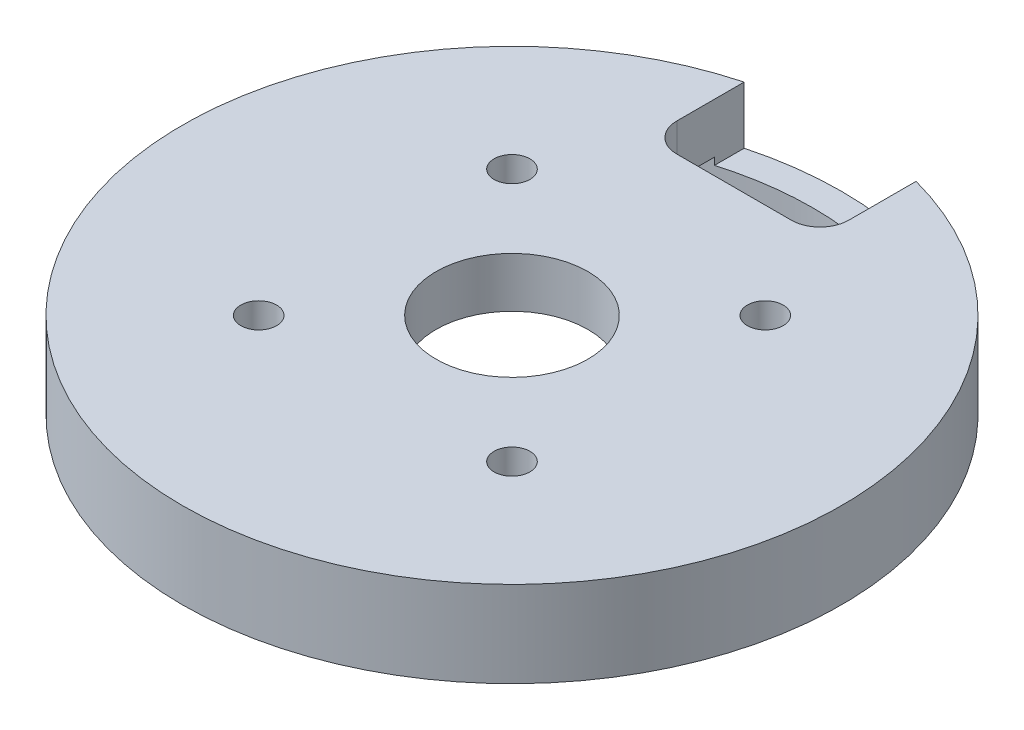
SolidWorks part; units mm, degrees
material "3.1355 (EN-AW 2024)"
ref_plane "Спереди" through (0, 0, 0) normal (0, 0, 1) x (1, 0, 0)
ref_plane "Сверху" through (0, 0, 0) normal (0, 1, 0) x (1, 0, 0)
ref_plane "Справа" through (0, 0, 0) normal (1, 0, 0) x (0, 0, -1)
sketch "Эскиз1" plane through (0, 0, 0) normal (0, 1, 0) x (1, 0, 0)
  circle A0 centre (0, 0) radius 23
  dimension "D1" = 46
extrude "Бобышка-Вытянуть1" add sketch "Эскиз1" along normal blind 6
sketch "Эскиз2" plane through (0, 0, 0) normal (0, -1, 0) x (1, 0, 0)
  circle A1 centre (0, 0) radius 5.3
  circle A2 centre (0, 0) radius 21
  circle A3 centre (0, 0) radius 21
  dimension "D2" = 10.6
  dimension "D1" = 2
extrude "Вырез-Вытянуть1" cut sketch "Эскиз2" against normal blind 2.5 contours A3 A1 | A1 region at (0, 0, 0) region at (-20.406, 0, 0)
extrude "Вырез-Вытянуть2" cut sketch "Эскиз2<3>" against normal through all contours A1 region at (0, 0, 0)
sketch "Эскиз2<3>" plane through (0, 0, 0) normal (0, -1, 0) x (1, 0, 0) same geometry as "Эскиз2"
sketch "Эскиз3" plane through (0, 6, 0) normal (0, 1, 0) x (1, 0, 0)
  line L0 (0, 0) -> (8.8388, 8.8388) construction
  line L1 (0, 0) -> (12.5, 0) construction
  line L2 (0, 0) -> (8.8388, -8.8388) construction
  line L3 (0, 0) -> (-8.8388, -8.8388) construction
  line L4 (0, 0) -> (-8.8388, 8.8388) construction
  circle A0 centre (0, 0) radius 12.5 construction
  point P11 (0, 0)
  dimension "D1" = 25
  dimension "D2" = 45
  dimension "D3" = 4
sketch "Эскиз4" plane through (0, 6, 0) normal (0, 1, 0) x (1, 0, 0)
  line L0 (0, 0) -> (0, 23) construction
  line L1 (-6, 22.2036) -> (-6, 17.5)
  line L2 (6, 22.2036) -> (6, 17.5)
  line L3 (0, 12.5) -> (0, 15.5) construction
  line L4 (-4, 15.5) -> (4, 15.5)
  circle A0 centre (0, 0) radius 23 construction
  arc A2 (4, 15.5) -> (6, 17.5) centre (4, 17.5) ccw
  arc A3 (-4, 15.5) -> (-6, 17.5) centre (-4, 17.5) cw
  circle A6 centre (0, 0) radius 23
  arc A7 (6, 22.2036) -> (-6, 22.2036) centre (0, 0) ccw
  point P13 (6, 10.9659)
  point P16 (-6, 10.9659)
  dimension "D2" = 2
  dimension "D1" = 6
  dimension "D4" = 3
  dimension "D3" = 0
extrude "Вырез-Вытянуть3" cut sketch "Эскиз4" against normal blind 4
hole_wizard "Отверстие обработанное метчиком M3x0.51" positions "Эскиз6" profile "Эскиз5" tap size "M3x0.5" standard "Ansi Metric" end condition through all
sketch "Эскиз6" plane through (0, 6, 0) normal (0, 1, 0) x (1, 0, 0)
  point P0 (-8.8388, 8.8388)
  point P3 (8.8388, 8.8388)
  point P6 (8.8388, -8.8388)
  point P9 (-8.8388, -8.8388)
sketch "Эскиз5" plane through (-8.8388, 6, -8.8388) normal (1, 0, 0) x (0, 0, 1)
  line L0 (0, 0) -> (0, 6)
  line L1 (0, 6) -> (1.25, 6)
  line L2 (1.25, 6) -> (1.25, 0)
  line L5 (1.25, 0) -> (0, 0)
  line L11 (0, -6.35) -> (0, 107.95) construction
  dimension "Диаметр проходного сверла" = 2.5
  dimension "Глубина проходного сверла" = 6
cosmetic thread "Отверстие резьбы1" parameters "D2"=3
cosmetic thread "Отверстие резьбы2" parameters "D2"=3
cosmetic thread "Отверстие резьбы3" parameters "D2"=3
cosmetic thread "Отверстие резьбы4" parameters "D2"=3
